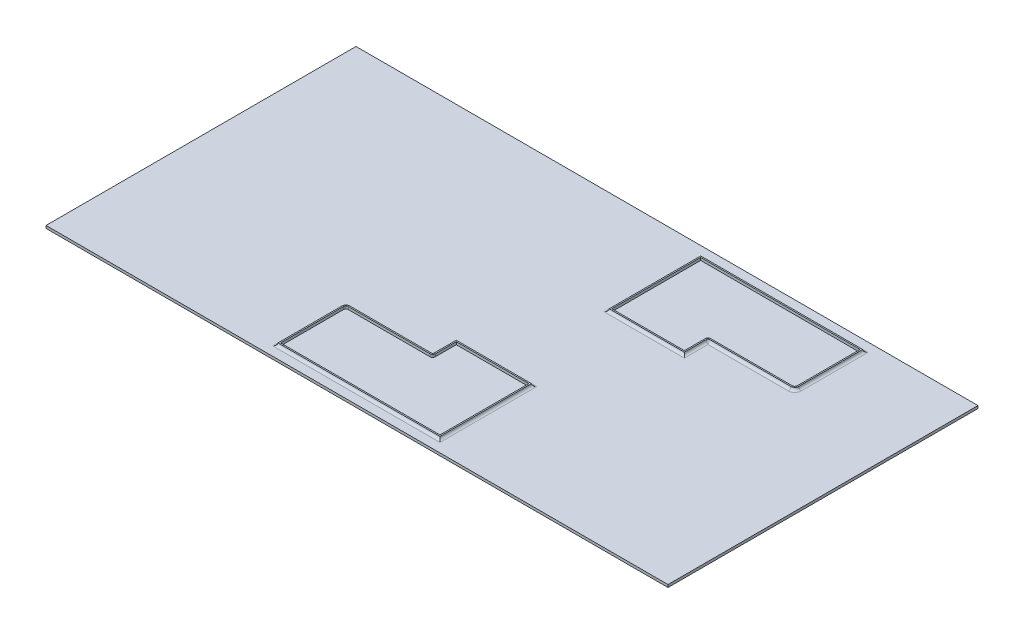
SolidWorks part; units mm, degrees
ref_plane "Front Plane" through (0, 0, 0) normal (0, 0, 1) x (1, 0, 0)
ref_plane "Top Plane" through (0, 0, 0) normal (0, 1, 0) x (1, 0, 0)
ref_plane "Right Plane" through (0, 0, 0) normal (1, 0, 0) x (0, 0, -1)
sketch "Sketch1" plane through (0, 287.2352, 0) normal (0, -1, 0) x (1, 0, 0)
  line L0 (295.5772, 2393.1549) -> (-319.3738, 2393.1549) construction
  line L1 (-1174.4228, 2443.1549) -> (1225.5772, 2443.1549)
  line L2 (-1174.4228, 2443.1549) -> (-1174.4228, 1246.9486)
  line L3 (-1174.4228, 1246.9486) -> (1225.5772, 1246.9486)
  line L4 (1225.5772, 2443.1549) -> (1225.5772, 1246.9486)
  line L5 (205.5772, 1296.9486) -> (820.5282, 1296.9486) construction
  line L6 (1175.5772, 2009.9506) -> (1175.5772, 1679.9506) construction
  line L7 (-674.4228, 2014.9506) -> (-674.4228, 1674.9506) construction
  dimension "D1" = 50
  dimension "D2" = 50
  dimension "D3" = 50
  dimension "D4" = 500
extrude "Bottom plate" add sketch "Sketch1" along normal blind 10
sketch "Sketch3" plane through (0, 287.2352, 0) normal (0, 1, 0) x (1, 0, 0)
  line L0 (15.5772, -2050.1529) -> (295.5772, -2050.1529) construction
  line L1 (15.5772, -2131.0779) -> (15.5772, -2050.1529) construction
  line L2 (-309.3738, -2141.0779) -> (5.5772, -2141.0779) construction
  line L3 (295.5772, -2050.1529) -> (295.5772, -2393.1549) construction
  line L4 (-319.3738, -2393.1549) -> (-319.3738, -2151.0779) construction
  line L5 (295.5772, -2393.1549) -> (-319.3738, -2393.1549) construction
  line L6 (15.5772, -2050.1529) -> (295.5772, -2050.1529)
  line L7 (15.5772, -2131.0779) -> (15.5772, -2050.1529)
  line L8 (-309.3738, -2141.0779) -> (5.5772, -2141.0779)
  line L9 (295.5772, -2050.1529) -> (295.5772, -2393.1549)
  line L10 (-319.3738, -2393.1549) -> (-319.3738, -2151.0779)
  line L11 (295.5772, -2393.1549) -> (-319.3738, -2393.1549)
  line L12 (205.5772, -1639.9506) -> (205.5772, -1296.9486) construction
  line L13 (205.5772, -1296.9486) -> (820.5282, -1296.9486) construction
  line L14 (820.5282, -1296.9486) -> (820.5282, -1539.0256) construction
  line L15 (810.5282, -1549.0256) -> (495.5772, -1549.0256) construction
  line L16 (485.5772, -1559.0256) -> (485.5772, -1639.9506) construction
  line L17 (485.5772, -1639.9506) -> (205.5772, -1639.9506) construction
  line L18 (205.5772, -1639.9506) -> (205.5772, -1296.9486)
  line L19 (205.5772, -1296.9486) -> (820.5282, -1296.9486)
  line L20 (820.5282, -1296.9486) -> (820.5282, -1539.0256)
  line L21 (810.5282, -1549.0256) -> (495.5772, -1549.0256)
  line L22 (485.5772, -1559.0256) -> (485.5772, -1639.9506)
  line L23 (485.5772, -1639.9506) -> (205.5772, -1639.9506)
  line L24 (200.5772, -1644.9506) -> (200.5772, -1291.9486)
  line L25 (200.5772, -1291.9486) -> (825.5282, -1291.9486)
  line L26 (825.5282, -1291.9486) -> (825.5282, -1539.0256)
  line L27 (810.5282, -1554.0256) -> (495.5772, -1554.0256)
  line L28 (490.5772, -1559.0256) -> (490.5772, -1644.9506)
  line L29 (490.5772, -1644.9506) -> (200.5772, -1644.9506)
  line L30 (10.5772, -2045.1529) -> (300.5772, -2045.1529)
  line L31 (300.5772, -2045.1529) -> (300.5772, -2398.1549)
  line L32 (300.5772, -2398.1549) -> (-324.3738, -2398.1549)
  line L33 (-324.3738, -2398.1549) -> (-324.3738, -2151.0779)
  line L34 (-309.3738, -2136.0779) -> (5.5772, -2136.0779)
  line L35 (10.5772, -2131.0779) -> (10.5772, -2045.1529)
  arc A0 (5.5772, -2141.0779) -> (15.5772, -2131.0779) centre (5.5772, -2131.0779) ccw construction
  arc A1 (-309.3738, -2141.0779) -> (-319.3738, -2151.0779) centre (-309.3738, -2151.0779) ccw construction
  arc A2 (5.5772, -2141.0779) -> (15.5772, -2131.0779) centre (5.5772, -2131.0779) ccw
  arc A3 (-309.3738, -2141.0779) -> (-319.3738, -2151.0779) centre (-309.3738, -2151.0779) ccw
  arc A4 (810.5282, -1549.0256) -> (820.5282, -1539.0256) centre (810.5282, -1539.0256) ccw construction
  arc A5 (495.5772, -1549.0256) -> (485.5772, -1559.0256) centre (495.5772, -1559.0256) ccw construction
  arc A6 (810.5282, -1549.0256) -> (820.5282, -1539.0256) centre (810.5282, -1539.0256) ccw
  arc A7 (495.5772, -1549.0256) -> (485.5772, -1559.0256) centre (495.5772, -1559.0256) ccw
  arc A8 (810.5282, -1554.0256) -> (825.5282, -1539.0256) centre (810.5282, -1539.0256) ccw
  arc A9 (495.5772, -1554.0256) -> (490.5772, -1559.0256) centre (495.5772, -1559.0256) ccw
  arc A10 (-309.3738, -2136.0779) -> (-324.3738, -2151.0779) centre (-309.3738, -2151.0779) ccw
  arc A11 (5.5772, -2136.0779) -> (10.5772, -2131.0779) centre (5.5772, -2131.0779) ccw
  dimension "D1" = 5
extrude "Elevator mechanism outlines" add sketch "Sketch3" along normal blind 10
fillet "Outline fillets" radius 10 16 edges at (825.5282, 287.2352, 1415.4871) (821.1348, 287.2352, 1549.6322) (653.0527, 287.2352, 1554.0256) (492.0417, 287.2352, 1555.4901) (10.5772, 287.2352, 2088.1154) (9.1127, 287.2352, 2134.6135) (-324.3738, 287.2352, 2274.6164) (-319.9804, 287.2352, 2140.4713) (490.5772, 287.2352, 1601.9881) (345.5772, 287.2352, 1644.9506) (200.5772, 287.2352, 1468.4496) (513.0527, 287.2352, 1291.9486) (-151.8983, 287.2352, 2136.0779) (155.5772, 287.2352, 2045.1529) (300.5772, 287.2352, 2221.6539) (-11.8983, 287.2352, 2398.1549)
